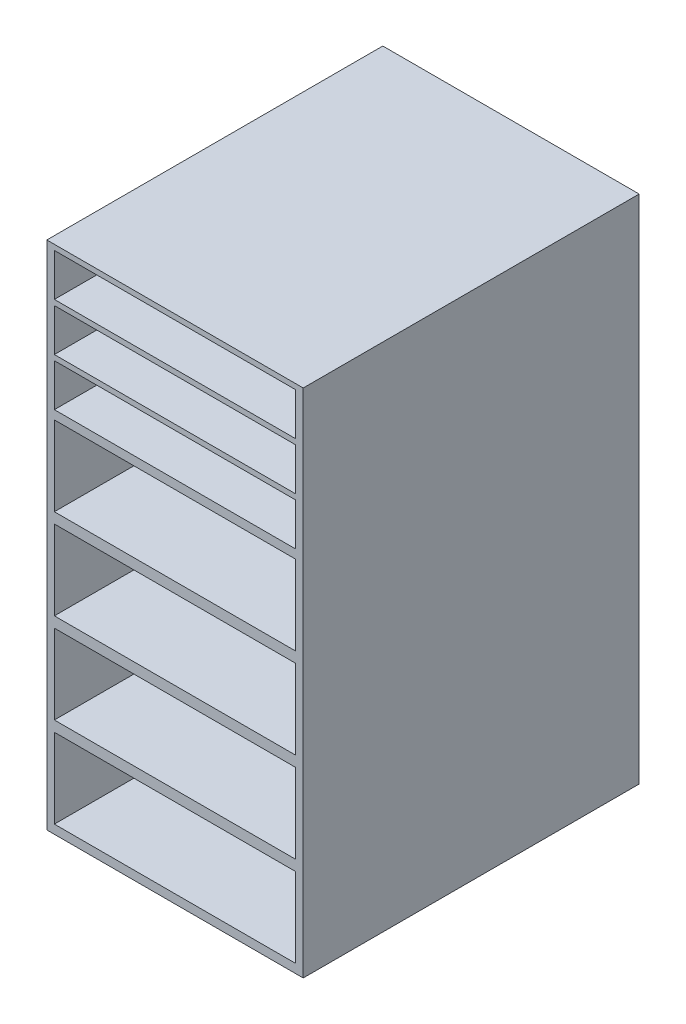
SolidWorks part; units mm, degrees
ref_plane "Front Plane" through (0, 0, 0) normal (0, 0, 1) x (1, 0, 0)
ref_plane "Top Plane" through (0, 0, 0) normal (0, 1, 0) x (1, 0, 0)
ref_plane "Right Plane" through (0, 0, 0) normal (1, 0, 0) x (0, 0, -1)
sketch "Sketch1" plane through (0, 0, 0) normal (0, 1, 0) x (1, 0, 0)
  line L1 (-36.25, -47.5) -> (36.25, -47.5)
  line L2 (-36.25, -47.5) -> (-36.25, 47.5)
  line L3 (-36.25, 47.5) -> (36.25, 47.5)
  line L4 (36.25, -47.5) -> (36.25, 47.5)
  line L5 (-36.25, -47.5) -> (36.25, 47.5) construction
  line L6 (-36.25, 47.5) -> (36.25, -47.5) construction
  point P0 (0, 0)
  dimension "D1" = 95
  dimension "D2" = 72.5
extrude "Boss-Extrude1" add sketch "Sketch1" along normal blind 104.5
sketch "Sketch2" plane through (0, 0, 47.5) normal (0, 0, 1) x (1, 0, 0)
  line L0 (0, 0) -> (0, 104.5) construction
  line L1 (-34.125, 2.5) -> (34.125, 2.5)
  line L2 (-34.125, 2.5) -> (-34.125, 25)
  line L3 (-34.125, 25) -> (34.125, 25)
  line L4 (34.125, 2.5) -> (34.125, 25)
  line L5 (-34.125, 2.5) -> (34.125, 25) construction
  line L6 (-34.125, 25) -> (34.125, 2.5) construction
  line L7 (-36.25, 104.5) -> (36.25, 104.5) construction
  line L8 (-36.25, 0) -> (36.25, 0) construction
  line L9 (-34.125, 28) -> (-34.125, 50.5)
  line L10 (-34.125, 28) -> (34.125, 28)
  line L11 (34.125, 28) -> (34.125, 50.5)
  line L12 (-34.125, 50.5) -> (34.125, 50.5)
  line L13 (-34.125, 53.5) -> (-34.125, 76)
  line L14 (-34.125, 53.5) -> (34.125, 53.5)
  line L15 (34.125, 53.5) -> (34.125, 76)
  line L16 (-34.125, 76) -> (34.125, 76)
  line L17 (-34.125, 79) -> (-34.125, 101.5)
  line L18 (-34.125, 79) -> (34.125, 79)
  line L19 (34.125, 79) -> (34.125, 101.5)
  line L20 (-34.125, 101.5) -> (34.125, 101.5)
  point P0 (0, 13.75)
  dimension "D1" = 68.25
  dimension "D2" = 22.5
  dimension "D3" = 2.5
  dimension "D4" = 4
extrude "Cut-Extrude1" cut sketch "Sketch2" against normal blind 90
sketch "Sketch3" plane through (0, 104.5, 0) normal (0, 1, 0) x (1, 0, 0)
  line L4 (36.25, -47.5) -> (36.25, 47.5)
  line L5 (36.25, 47.5) -> (-36.25, 47.5)
  line L6 (-36.25, 47.5) -> (-36.25, -47.5)
  line L7 (-36.25, -47.5) -> (36.25, -47.5)
  line L8 (36.25, -47.5) -> (36.25, 47.5)
  line L9 (36.25, 47.5) -> (-36.25, 47.5)
  line L10 (-36.25, 47.5) -> (-36.25, -47.5)
  line L11 (-36.25, -47.5) -> (36.25, -47.5)
  dimension "D1" = 0
extrude "Boss-Extrude2" add sketch "Sketch3" along normal blind 175.5
sketch "Sketch4" plane through (0, 0, 47.5) normal (0, 0, 1) x (1, 0, 0)
  line L0 (0, 0) -> (0, 280) construction
  line L1 (-36.25, 280) -> (36.25, 280) construction
  line L2 (34.125, 101.5) -> (-34.125, 101.5) construction
  line L3 (-34.125, 104) -> (34.125, 104)
  line L4 (-34.125, 104) -> (-34.125, 116)
  line L5 (-34.125, 116) -> (34.125, 116)
  line L6 (34.125, 104) -> (34.125, 116)
  line L7 (-34.125, 104) -> (34.125, 116) construction
  line L8 (-34.125, 116) -> (34.125, 104) construction
  line L9 (-34.125, 117.5) -> (-34.125, 129.5)
  line L10 (-34.125, 117.5) -> (34.125, 117.5)
  line L11 (34.125, 117.5) -> (34.125, 129.5)
  line L12 (-34.125, 129.5) -> (34.125, 129.5)
  line L13 (-34.125, 131) -> (-34.125, 143)
  line L14 (-34.125, 131) -> (34.125, 131)
  line L15 (34.125, 131) -> (34.125, 143)
  line L16 (-34.125, 143) -> (34.125, 143)
  line L17 (-34.125, 144.5) -> (-34.125, 156.5)
  line L18 (-34.125, 144.5) -> (34.125, 144.5)
  line L19 (34.125, 144.5) -> (34.125, 156.5)
  line L20 (-34.125, 156.5) -> (34.125, 156.5)
  line L21 (-34.125, 158) -> (-34.125, 170)
  line L22 (-34.125, 158) -> (34.125, 158)
  line L23 (34.125, 158) -> (34.125, 170)
  line L24 (-34.125, 170) -> (34.125, 170)
  line L25 (-34.125, 171.5) -> (-34.125, 183.5)
  line L26 (-34.125, 171.5) -> (34.125, 171.5)
  line L27 (34.125, 171.5) -> (34.125, 183.5)
  line L28 (-34.125, 183.5) -> (34.125, 183.5)
  line L29 (-34.125, 185) -> (-34.125, 197)
  line L30 (-34.125, 185) -> (34.125, 185)
  line L31 (34.125, 185) -> (34.125, 197)
  line L32 (-34.125, 197) -> (34.125, 197)
  line L33 (-34.125, 198.5) -> (-34.125, 210.5)
  line L34 (-34.125, 198.5) -> (34.125, 198.5)
  line L35 (34.125, 198.5) -> (34.125, 210.5)
  line L36 (-34.125, 210.5) -> (34.125, 210.5)
  line L37 (-34.125, 212) -> (-34.125, 224)
  line L38 (-34.125, 212) -> (34.125, 212)
  line L39 (34.125, 212) -> (34.125, 224)
  line L40 (-34.125, 224) -> (34.125, 224)
  line L41 (-34.125, 225.5) -> (-34.125, 237.5)
  line L42 (-34.125, 225.5) -> (34.125, 225.5)
  line L43 (34.125, 225.5) -> (34.125, 237.5)
  line L44 (-34.125, 237.5) -> (34.125, 237.5)
  line L45 (-34.125, 239) -> (-34.125, 251)
  line L46 (-34.125, 239) -> (34.125, 239)
  line L47 (34.125, 239) -> (34.125, 251)
  line L48 (-34.125, 251) -> (34.125, 251)
  line L49 (-34.125, 252.5) -> (-34.125, 264.5)
  line L50 (-34.125, 252.5) -> (34.125, 252.5)
  line L51 (34.125, 252.5) -> (34.125, 264.5)
  line L52 (-34.125, 264.5) -> (34.125, 264.5)
  line L53 (-34.125, 266) -> (-34.125, 278)
  line L54 (-34.125, 266) -> (34.125, 266)
  line L55 (34.125, 266) -> (34.125, 278)
  line L56 (-34.125, 278) -> (34.125, 278)
  point P5 (0, 110)
  dimension "D1" = 68.25
  dimension "D2" = 12
  dimension "D3" = 2.5
  dimension "D4" = 13
extrude "Cut-Extrude3" cut sketch "Sketch4" against normal blind 90
split "Split1" bodies to split 105 resulting bodies 126 split by face at (0, 144.5, 2.5)
